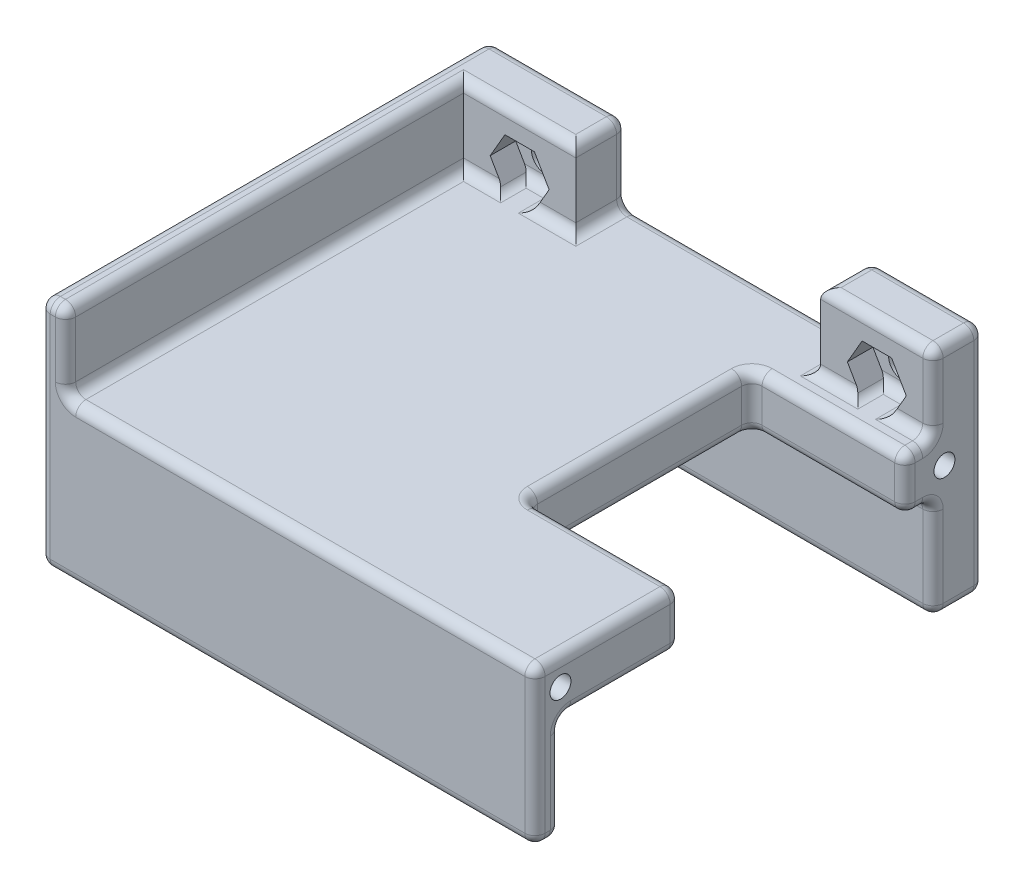
SolidWorks part; units mm, degrees
material "ABS"
ref_plane "Front Plane" through (0, 0, 0) normal (0, 0, 1) x (1, 0, 0)
ref_plane "Top Plane" through (0, 0, 0) normal (0, 1, 0) x (1, 0, 0)
ref_plane "Right Plane" through (0, 0, 0) normal (1, 0, 0) x (0, 0, -1)
sketch "Sketch16" plane through (0, 0, 0) normal (0, 0, 1) x (1, 0, 0)
  line L0 (-17.5, 0) -> (17.5, 0) construction
  line L2 (-16.0566, 2.5) -> (-18.9434, 2.5)
  line L3 (-18.9434, 2.5) -> (-20.3868, 0)
  line L4 (-20.3868, 0) -> (-18.9434, -2.5)
  line L5 (-18.9434, -2.5) -> (-16.0566, -2.5)
  line L6 (-16.0566, -2.5) -> (-14.6132, 0)
  line L7 (-14.6132, 0) -> (-16.0566, 2.5)
  line L8 (18.9434, 2.5) -> (16.0566, 2.5)
  line L9 (16.0566, 2.5) -> (14.6132, 0)
  line L10 (14.6132, 0) -> (16.0566, -2.5)
  line L11 (16.0566, -2.5) -> (18.9434, -2.5)
  line L12 (18.9434, -2.5) -> (20.3868, 0)
  line L13 (20.3868, 0) -> (18.9434, 2.5)
  line L14 (-23, 5) -> (-12, 5)
  line L15 (-23, 5) -> (-23, -2.5)
  line L16 (-23, -2.5) -> (-12, -2.5)
  line L17 (-12, 5) -> (-12, -2.5)
  line L18 (12, 5) -> (23, 5)
  line L19 (12, 5) -> (12, -2.5)
  line L20 (12, -2.5) -> (23, -2.5)
  line L21 (23, 5) -> (23, -2.5)
  line L22 (-23, 5) -> (-25.5, 5)
  line L23 (-23, 5) -> (-23, -17.8)
  line L24 (-23, -17.8) -> (-25.5, -17.8)
  line L25 (-25.5, 5) -> (-25.5, -17.8)
  line L26 (-23, -2.5) -> (23, -2.5)
  line L27 (-23, -2.5) -> (-23, -7.8)
  line L28 (-23, -7.8) -> (23, -7.8)
  line L29 (23, -2.5) -> (23, -7.8)
  line L30 (-23, -17.8) -> (23, -17.8)
  line L31 (-23, -17.8) -> (-23, -7.8)
  line L32 (-23, -7.8) -> (23, -7.8)
  line L33 (23, -17.8) -> (23, -7.8)
  line L34 (23, 5) -> (25.5, 5) construction
  line L35 (23, 5) -> (23, -17.8) construction
  line L36 (23, -17.8) -> (25.5, -17.8) construction
  line L37 (25.5, 5) -> (25.5, -17.8) construction
  line L38 (25.5, 5) -> (28.5, 5) construction
  line L39 (25.5, 5) -> (25.5, -17.8) construction
  line L40 (25.5, -17.8) -> (28.5, -17.8) construction
  line L41 (28.5, 5) -> (28.5, -17.8) construction
  circle A0 centre (-17.5, 0) radius 2.5 construction
  circle A1 centre (17.5, 0) radius 2.5 construction
  point P4 (0, 0)
  point P28 (17.5, 5)
  point P30 (-17.5, 5)
  dimension "D1" = 35
  dimension "D2" = 5
  dimension "D3" = 46
  dimension "D4" = 2.5
  dimension "D5" = 7.8
  dimension "D6" = 2.5
  dimension "D7" = 2.5
  dimension "D8" = 10
  dimension "D9" = 3
extrude "Boss-Extrude1" add sketch "Sketch16" along normal blind 5 contours L17 L14 L15 L16 L4 L3 L2 L7 L6 | L21 L18 L19 L20 L10 L9 L8 L13 L12 | L23 L22 L25 L24 | L27 L26 L29 L28 | L31 L30 L33 L32 | L2 L3 L4 L5 L6 L7 | L19 L18 L21 L20 region at (-17.5, 2.6331, 0) region at (12.1331, 1.25, 0)
extrude "Cut-Extrude4" cut sketch "Sketch16<5>" against normal blind 2.5 from surface contours L6 L7 L2 L3 L4 L5 | L12 L13 L8 L9 L10 L11 region at (-17.5, 0, 0) region at (17.5, 0, 0) starting at face at (-0.625, -2.575, 5)
sketch "Sketch16<5>" plane through (0, 0, 0) normal (0, 0, 1) x (1, 0, 0) same geometry as "Sketch16"
extrude "Boss-Extrude2" add sketch "Sketch16<4>" along normal blind 41.5 contours L22 L25 L24 L23 L15 | L29 L20 L11 L26 L16 L5 L23 L28 region at (0, -5.15, 0) region at (-24.25, -6.4, 0)
sketch "Sketch16<4>" plane through (0, 0, 0) normal (0, 0, 1) x (1, 0, 0) same geometry as "Sketch16"
extrude "Boss-Extrude3" add sketch "Sketch16<6>" along normal blind 2.5 from surface contours L29 L20 L11 L26 L16 L5 L23 L28 | L22 L25 L24 L23 L15 | L30 L33 L28 L23 region at (0, -5.15, 0) region at (-24.25, -6.4, 0) region at (0, -12.8, 0) starting at face at (-12.125, -5.775, 41.5)
sketch "Sketch16<6>" plane through (0, 0, 0) normal (0, 0, 1) x (1, 0, 0) same geometry as "Sketch16"
sketch "Sketch17" plane through (0, -2.5, 0) normal (0, 1, 0) x (1, 0, 0)
  line L0 (23, -44) -> (23, -5) construction
  line L1 (23, -7.75) -> (8, -7.75)
  line L2 (23, -7.75) -> (23, -29.75)
  line L3 (23, -29.75) -> (8, -29.75)
  line L4 (8, -7.75) -> (8, -29.75)
  line L5 (23, -5) -> (18.9434, -5) construction
  dimension "D1" = 15
  dimension "D2" = 22
  dimension "D3" = 2.75
extrude "Cut-Extrude5" cut sketch "Sketch17" against normal through all
sketch "Sketch18" plane through (23, 0, 0) normal (1, 0, 0) x (0, 0, -1)
  line L0 (-41.5, -5.15) -> (-3.875, -5.15) construction
  line L1 (-29.75, -7.8) -> (-29.75, -2.5) construction
  line L2 (-44, -17.8) -> (-44, -2.5) construction
  line L3 (0, 5) -> (0, -17.8) construction
  line L4 (-7.75, -7.8) -> (-7.75, -2.5) construction
  point P0 (-41.5, -5.15)
  point P1 (-3.875, -5.15)
  point P4 (-29.75, -5.15)
  point P13 (-3.875, -5.15)
  point P15 (-41.5, -5.15)
  dimension "D1" = 2.5
  dimension "D2" = 3.875
  dimension "D3" = 7.75
hole_wizard "M2.5x0.45 Tapped Hole2" positions "Sketch18" profile "Sketch19" tap size "M2.5x0.45" standard "ANSI Metric"
sketch "Sketch19" plane through (23, -5.15, 41.5) normal (0, 1, 0) x (0, 0, -1)
  line L0 (0, 0) -> (0, 15.6159)
  line L1 (0, 15.6159) -> (1.025, 15)
  line L2 (1.025, 15) -> (1.025, 0)
  line L5 (1.025, 0) -> (0, 0)
  line L10 (0, 15.6159) -> (-1.025, 15) construction
  line L11 (0, -6.35) -> (0, 107.95) construction
  dimension "Tap Drill Dia." = 2.05
  dimension "Tap Drill Depth" = 15
  dimension "Drill Angle" = 118
cosmetic thread "Hole Thread3" parameters "D1"=5, "D2"=2.5
cosmetic thread "Hole Thread4" parameters "D1"=5, "D2"=2.5
sketch "Sketch20" plane through (0, 0, 0) normal (0, 0, -1) x (-1, 0, 0)
  point P0 (-17.5, 0)
  point P3 (17.5, 0)
fillet "Fillet1" radius 1 62 edges at (-23, 1.25, 44) (-12, 1.25, 0) (12, 1.25, 0) (23, 1.25, 5) (23, -2.5, 36.875) (0, -2.5, 44) (-23, -2.5, 24.5) (-20.9717, -2.5, 5) (-18.9434, -2.5, 3.75) (-17.5, -2.5, 2.5) (-16.0566, -2.5, 3.75) (-14.0283, -2.5, 5) (-12, -2.5, 2.5) (0, -2.5, 0) (12, -2.5, 2.5) (14.0283, -2.5, 5) (16.0566, -2.5, 3.75) (17.5, -2.5, 2.5) (18.9434, -2.5, 3.75) (20.9717, -2.5, 5) (23, -2.5, 6.375) (15.5, -2.5, 7.75) (8, -2.5, 18.75) (15.5, -2.5, 29.75) (23, -12.8, 5) (23, -12.8, 41.5) (0, -17.8, 41.5) (0, -17.8, 5) (15.5, -7.8, 7.75) (23, -7.8, 6.375) (0, -7.8, 5) (0, -7.8, 41.5) (23, -7.8, 35.625) (15.5, -7.8, 29.75) (-23, -12.8, 41.5) (-23, -7.8, 23.25) (-23, -12.8, 5) (-23, -17.8, 23.25) (8, -7.8, 18.75) (8, -5.15, 29.75) (8, -5.15, 7.75) (23, 5, 2.5) (17.5, 5, 5) (12, 5, 2.5) (17.5, 5, 0) (-17.5, 5, 5) (-23, 5, 24.5) (-24.25, 5, 44) (-25.5, 5, 22) (-18.75, 5, 0) (-12, 5, 2.5) (23, -17.8, 42.75) (23, -10.15, 44) (23, -5.15, 29.75) (-1.25, -17.8, 44) (-25.5, -6.4, 44) (-25.5, -6.4, 0) (23, -6.4, 0) (23, -17.8, 2.5) (-1.25, -17.8, 0) (-25.5, -17.8, 22) (23, -5.15, 7.75)
hole_wizard "M2.5 Clearance Hole1" positions "Sketch20" profile "Sketch21" hole size "M2.5" standard "ANSI Metric" end condition through all
sketch "Sketch21" plane through (17.5, 0, 0) normal (1, 0, 0) x (0, 1, 0)
  line L0 (0, 0) -> (0, 44)
  line L1 (0, 44) -> (1.35, 44)
  line L2 (1.35, 44) -> (1.35, 0)
  line L5 (1.35, 0) -> (0, 0)
  line L11 (0, -6.35) -> (0, 107.95) construction
  dimension "Thru Hole Dia." = 2.7
  dimension "Thru Hole Depth" = 44
equation "\"D2@Sketch18\"=\"D3@Sketch18\"/2"
